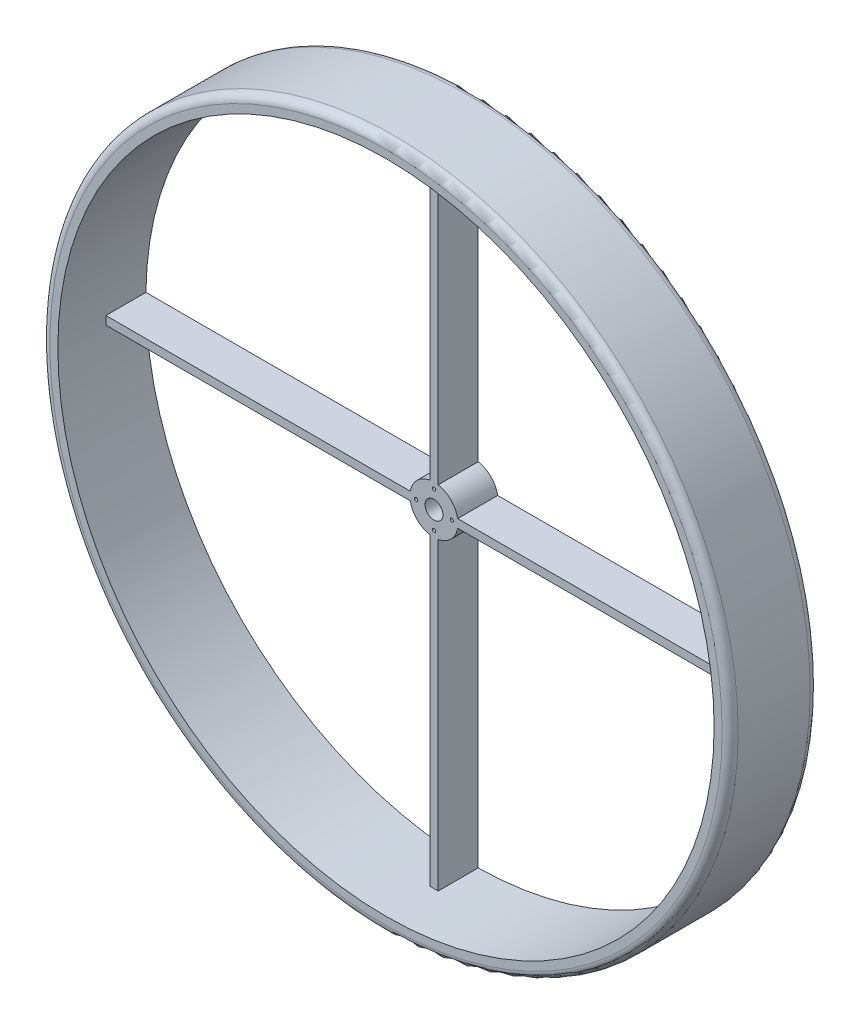
SolidWorks part; units mm, degrees
ref_plane "Front Plane" through (0, 0, 0) normal (0, 0, 1) x (1, 0, 0)
ref_plane "Top Plane" through (0, 0, 0) normal (0, 1, 0) x (1, 0, 0)
ref_plane "Right Plane" through (0, 0, 0) normal (1, 0, 0) x (0, 0, -1)
sketch "Sketch2" plane through (0, 0, 0) normal (0, 0, 1) x (1, 0, 0)
  circle A0 centre (0, 0) radius 215
  circle A1 centre (0, 0) radius 205
  dimension "D1" = 430
  dimension "D2" = 410
extrude "Boss-Extrude1" add sketch "Sketch2" along normal blind 50 and the other way blind 5
sketch "Sketch3" plane through (0, 0, 0) normal (0, 0, 1) x (1, 0, 0)
  line L0 (0, 108.9139) -> (0, -118.2452) construction
  line L1 (-114.1628, 0) -> (113.5796, 0) construction
  line L2 (0, 0) -> (-5.5149, 0.9724)
  line L3 (0, 0) -> (-5.5149, -0.9724)
  line L4 (0, 0) -> (5.5149, -0.9724)
  line L5 (0, 0) -> (5.5149, 0.9724)
  line L6 (0, 0) -> (-96.8124, 96.8124) construction
  line L7 (0, 0) -> (-0.9724, 5.5149)
  line L8 (0, 0) -> (0.9724, 5.5149)
  line L9 (0, 0) -> (0.9724, -5.5149)
  line L10 (0, 0) -> (-0.9724, -5.5149)
  line L11 (14.7721, 2.6047) -> (210.9761, 2.6047)
  line L12 (14.7721, -2.6047) -> (210.9761, -2.6047)
  line L13 (210.9761, -2.6047) -> (210.9761, 2.6047)
  line L14 (-14.7721, -2.6047) -> (-210.9761, -2.6047)
  line L16 (-14.7721, 2.6047) -> (-210.9761, 2.6047)
  line L17 (-210.9761, -2.6047) -> (-210.9761, 2.6047)
  line L18 (2.6047, 210.9761) -> (-2.6047, 210.9761)
  line L19 (2.6047, 14.7721) -> (2.6047, 210.9761)
  line L21 (-2.6047, 14.7721) -> (-2.6047, 210.9761)
  line L22 (-2.6047, -14.7721) -> (-2.6047, -210.9761)
  line L23 (2.6047, -210.9761) -> (-2.6047, -210.9761)
  line L24 (2.6047, -14.7721) -> (2.6047, -210.9761)
  arc A0 (-2.6047, 14.7721) -> (-14.7721, 2.6047) centre (0, 0) ccw
  circle A1 centre (0, 0) radius 5.6
  arc A3 (-14.7721, -2.6047) -> (-2.6047, -14.7721) centre (0, 0) ccw
  arc A4 (2.6047, -14.7721) -> (14.7721, -2.6047) centre (0, 0) ccw
  arc A5 (14.7721, 2.6047) -> (2.6047, 14.7721) centre (0, 0) ccw
  circle A6 centre (11.2, 0) radius 1
  circle A7 centre (-11.2, 0) radius 1
  circle A8 centre (0, -11.2) radius 1
  circle A9 centre (0, 11.2) radius 1
  dimension "D1" = 30
  dimension "D2" = 11.2
  dimension "D5" = 2
  dimension "D3" = 10
  dimension "D4" = 45
  dimension "D6" = 11.2
extrude "Boss-Extrude2" add sketch "Sketch3" along normal blind 20 and the other way blind 5 contours A5 L21 A0 A3 L24 A4 A1 region at (112.8741, 2.008, 0)
fillet "Fillet1" radius 5 1 edges at (215, 0, 50)
fillet "Fillet2" radius 5 1 edges at (215, 0, -5)
scale "Scale1" bodies to scale 102 scale about origin uniform scaling yes scale factor 0.625
